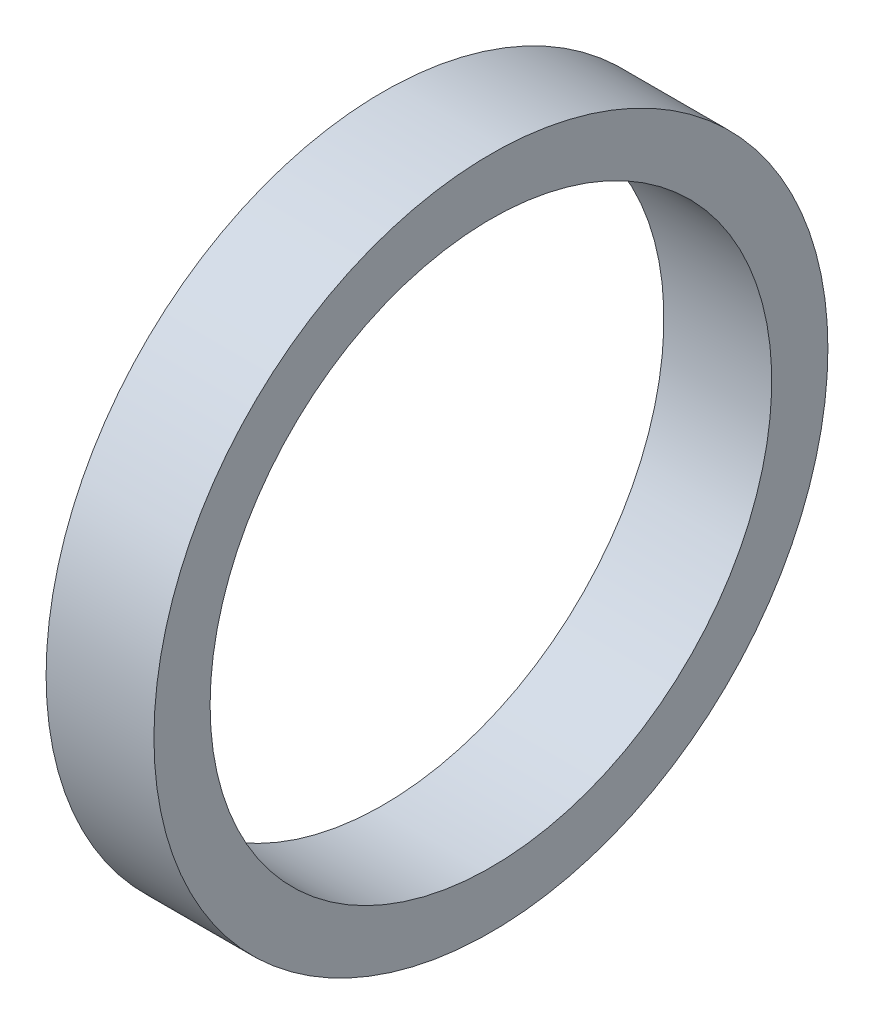
SolidWorks part; units mm, degrees
material "AISI 1020 Steel, Cold Rolled"
ref_plane "Front Plane" through (0, 0, 0) normal (0, 0, 1) x (1, 0, 0)
ref_plane "Top Plane" through (0, 0, 0) normal (0, 1, 0) x (1, 0, 0)
ref_plane "Right Plane" through (0, 0, 0) normal (1, 0, 0) x (0, 0, -1)
sketch "Sketch1" plane through (0, 0, 0) normal (1, 0, 0) x (0, 0, -1)
  circle A0 centre (0, 0) radius 7.9375
  circle A1 centre (0, 0) radius 9.525
  dimension "D1" = 15.875
  dimension "D2" = 19.05
extrude "Boss-Extrude1" add sketch "Sketch1" along normal blind 3.048
